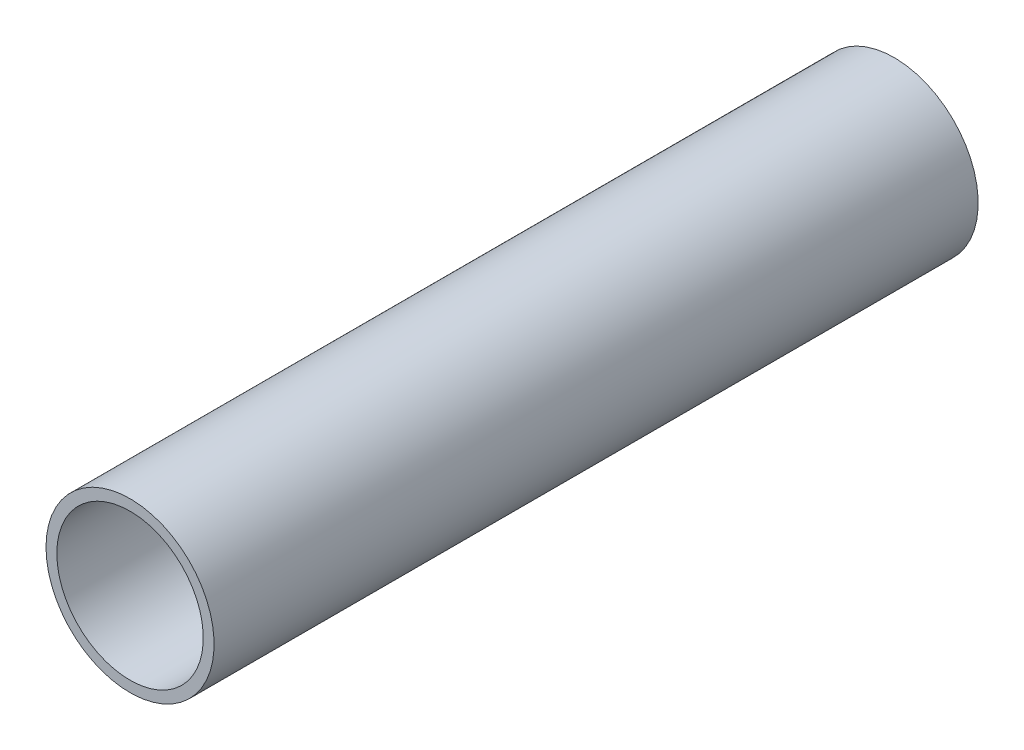
SolidWorks part; units mm, degrees
material "PVC Rigid"
ref_plane "Front Plane" through (0, 0, 0) normal (0, 0, 1) x (1, 0, 0)
ref_plane "Top Plane" through (0, 0, 0) normal (0, 1, 0) x (1, 0, 0)
ref_plane "Right Plane" through (0, 0, 0) normal (1, 0, 0) x (0, 0, -1)
sketch "Sketch1" plane through (0, 0, 0) normal (0, 0, 1) x (1, 0, 0)
  circle A0 centre (0, 0) radius 16.764
  circle A1 centre (0, 0) radius 14.605
  dimension "D1" = 33.528
  dimension "D2" = 29.21
extrude "Boss-Extrude1" add sketch "Sketch1" along normal blind 152.4
